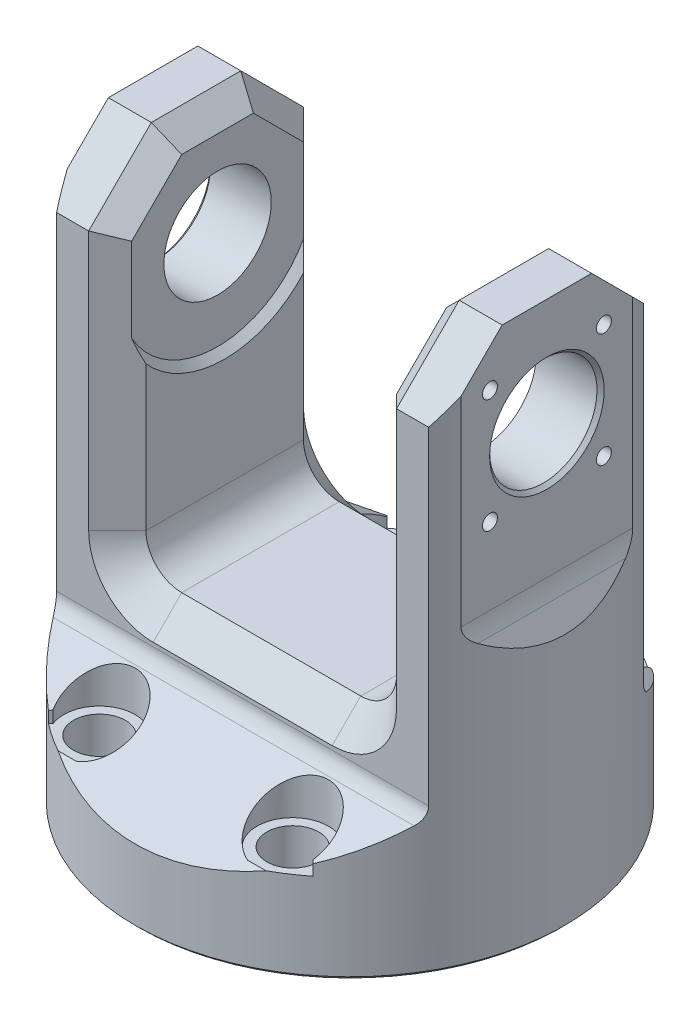
SolidWorks part; units mm, degrees
material "Cast Alloy Steel"
ref_plane "Front Plane" through (0, 0, 0) normal (0, 0, 1) x (1, 0, 0)
ref_plane "Top Plane" through (0, 0, 0) normal (0, 1, 0) x (1, 0, 0)
ref_plane "Right Plane" through (0, 0, 0) normal (1, 0, 0) x (0, 0, -1)
sketch "Sketch1" plane through (0, 0, 0) normal (0, 1, 0) x (1, 0, 0)
  circle A0 centre (0, 0) radius 60
  dimension "D1" = 120
extrude "Boss-Extrude1" add sketch "Sketch1" along normal blind 150
sketch "Sketch2" plane through (0, 0, 0) normal (0, 0, 1) x (1, 0, 0)
  line L0 (0, 150) -> (0, 0) construction
  line L2 (60, 150) -> (-60, 150) construction
  line L3 (-60, 0) -> (60, 0) construction
  line L4 (-35, 150) -> (-35, 50)
  line L5 (-35, 50) -> (35, 50)
  line L6 (35, 50) -> (35, 150)
  line L7 (-55, 150) -> (-55, 80)
  line L8 (-55, 80) -> (-60, 71.3397)
  line L9 (-60, 150) -> (-60, 0) construction
  line L10 (-35, 150) -> (35, 150)
  line L11 (-60, 71.3397) -> (-60, 150)
  line L12 (-60, 150) -> (-55, 150)
  line L13 (55, 80) -> (60, 71.3397)
  line L14 (60, 150) -> (55, 150)
  line L15 (55, 150) -> (55, 80)
  line L16 (60, 71.3397) -> (60, 150)
  dimension "D1" = 70
  dimension "D2" = 100
  dimension "D3" = 70
  dimension "D4" = 30
  dimension "D5" = 110
extrude "Cut-Extrude1" cut sketch "Sketch2" against normal through all both and the other way through all
fillet "Fillet1" radius 10 4 edges at (-35, 50, 0) (35, 50, 0) (-55, 80, 0) (55, 80, 0)
sketch "Sketch3" plane through (0, 0, 0) normal (1, 0, 0) x (0, 0, -1)
  line L0 (0, 150) -> (0, 0) construction
  line L1 (23.9792, 150) -> (-23.9792, 150) construction
  line L2 (-12.5, 150) -> (-30, 132.5)
  line L3 (12.5, 150) -> (30, 132.5)
  line L4 (-30, 132.5) -> (-30, 40.8868)
  line L5 (30, 132.5) -> (30, 40.8868)
  line L6 (-32.5, 36.5566) -> (-60, 20.6795)
  line L8 (32.5, 36.5566) -> (60, 20.6795)
  line L9 (-60, 20.6795) -> (-60, 0)
  line L10 (60, 20.6795) -> (60, 0)
  line L11 (-12.5, 150) -> (12.5, 150)
  line L12 (-60, 0) -> (60, 0)
  arc A0 (30, 40.8868) -> (32.5, 36.5566) centre (35, 40.8868) ccw
  arc A1 (-30, 40.8868) -> (-32.5, 36.5566) centre (-35, 40.8868) cw
  point P13 (-60, 14.4069)
  point P14 (-30, 44.3608)
  point P18 (-60, 25)
  point P21 (30, 38)
  point P24 (-30, 38)
  dimension "D6" = 5
  dimension "D1" = 25
  dimension "D2" = 60
  dimension "D3" = 45
  dimension "D4" = 38
  dimension "D5" = 30
extrude "Cut-Extrude2" cut sketch "Sketch3" against normal through all both and the other way through all flip side to cut
sketch "Sketch4" plane through (55, 0, 0) normal (1, 0, 0) x (0, 0, -1)
  line L0 (12.5, 150) -> (-12.5, 150) construction
  line L1 (0, 120) -> (0, 0) construction
  circle A0 centre (0, 120) radius 15
  dimension "D2" = 30
  dimension "D1" = 30
extrude "Cut-Extrude3" cut sketch "Sketch4" against normal through all both and the other way through all
sketch "Sketch5" plane through (55, 0, 0) normal (1, 0, 0) x (0, 0, -1)
  line L0 (0, 142.5) -> (0, 120) construction
  line L1 (0, 120) -> (15.9099, 135.9099) construction
  circle A0 centre (0, 120) radius 22.5 construction
  dimension "D1" = 45
  dimension "D2" = 45
hole_wizard "M5 Tapped Hole1" positions "3DSketch1" profile "Sketch6" tap size "M5" standard "ISO"
sketch3d "3DSketch1"
  point P0 (55, 135.9099, -15.9099)
sketch "Sketch6" plane through (55, 135.9099, -15.9099) normal (0, 1, 0) x (0, 0, -1)
  line L0 (0, 0) -> (0, 17.2618)
  line L1 (0, 17.2618) -> (2.1, 16)
  line L2 (2.1, 16) -> (2.1, 0)
  line L5 (2.1, 0) -> (0, 0)
  line L10 (0, 17.2618) -> (-2.1, 16) construction
  line L11 (0, -6.35) -> (0, 107.95) construction
  dimension "Tap Drill Dia." = 4.2
  dimension "Tap Drill Depth" = 16
  dimension "Drill Angle" = 118
cosmetic thread "Hole Thread1" parameters "D1"=12, "D2"=5
pattern_circular "CirPattern1" count 4 over 360 about axis through (0, 120, 0) along (1, 0, 0) of "M5 Tapped Hole1"
cosmetic thread "Hole Thread2" parameters "D1"=12, "D2"=5
cosmetic thread "Hole Thread3" parameters "D1"=12, "D2"=5
cosmetic thread "Hole Thread4" parameters "D1"=12, "D2"=5
mirror "Mirror1" about plane through (0, 0, 0) normal (1, 0, 0) of "M5 Tapped Hole1", "CirPattern1"
cosmetic thread "Hole Thread5" parameters "D1"=12, "D2"=5
cosmetic thread "Hole Thread6" parameters "D1"=12, "D2"=5
cosmetic thread "Hole Thread7" parameters "D1"=12, "D2"=5
cosmetic thread "Hole Thread8" parameters "D1"=12, "D2"=5
chamfer "Chamfer1" distance 8 angle 45 16 edges at (-35, 96.25, 30) (-35, 141.25, 21.25) (-35, 150, 0) (-35, 141.25, -21.25) (-35, 96.25, -30) (-32.0711, 52.9289, -30) (-32.0711, 52.9289, 30) (0, 50, -30) (0, 50, 30) (32.0711, 52.9289, -30) (32.0711, 52.9289, 30) (35, 96.25, -30) (35, 96.25, 30) (35, 141.25, 21.25) (35, 150, 0) (35, 141.25, -21.25)
sketch "Sketch9" plane through (0, 50, 0) normal (0, 1, 0) x (1, 0, 0)
  line L1 (-27, -43) -> (27, -43) construction
  line L2 (-27, -43) -> (-27, 43) construction
  line L3 (-27, 43) -> (27, 43) construction
  line L4 (27, -43) -> (27, 43) construction
  line L5 (-27, -43) -> (27, 43) construction
  line L6 (-27, 43) -> (27, -43) construction
  point P0 (0, 0)
  dimension "D1" = 86
  dimension "D2" = 54
hole_wizard "Hole1" positions "3DSketch4" profile "Sketch11" legacy end condition through all
sketch3d "3DSketch4"
  point P0 (-27, 50, -43)
  point P3 (27, 50, -43)
  point P6 (-27, 50, 43)
  point P9 (27, 50, 43)
sketch "Sketch11" plane through (-27, 50, -43) normal (1, 0, 0) x (0, 0, 1)
  line L0 (0, 0) -> (0, 50)
  line L1 (0, 50) -> (7.25, 50)
  line L2 (7.25, 50) -> (7.25, 25)
  line L3 (7.25, 25) -> (10, 25)
  line L4 (10, 25) -> (10, 0)
  line L5 (10, 0) -> (0, 0)
  line L6 (0, 110) -> (0, -10) construction
  dimension "Diameter" = 14.5
  dimension "Depth" = 50
  dimension "C-Bore Diameter" = 20
  dimension "C-Bore Depth" = 25
chamfer "Chamfer3" distance 1 angle 45 1 edges at (0, 0, 60)
chamfer "Chamfer4" distance 1 angle 45 2 edges at (55, 105, 0) (-55, 135, 0)
chamfer "Chamfer5" distance 2 2 edges at (35.3774, 26.1709, -48.4607) (-35.3774, 26.1709, -48.4607)
chamfer "Chamfer6" distance 2 2 edges at (-35.3774, 26.1709, 48.4607) (35.3774, 26.1709, 48.4607)
sketch "Sketch12" plane through (0, 0, 0) normal (0, 0, 1) x (1, 0, 0)
  line L0 (37, 147.5) -> (37, 120)
  line L1 (37, 120) -> (32, 120)
  line L2 (32, 120) -> (32, 152.5)
  line L3 (32, 152.5) -> (37, 147.5)
  line L4 (0, 50) -> (0, 172.6219) construction
  line L5 (-25, 50) -> (25, 50) construction
  line L6 (37, 120) -> (54, 120) construction
  line L8 (54, 105) -> (54, 135) construction
  point P12 (32, 153.4708)
  dimension "D1" = 74
  dimension "D2" = 45
  dimension "D3" = 27.5
  dimension "D4" = 5
revolve "Cut-Revolve1" cut sketch "Sketch12" angle 360 about L1
mirror "Mirror2" about plane through (0, 0, 0) normal (1, 0, 0) of "Cut-Revolve1"
